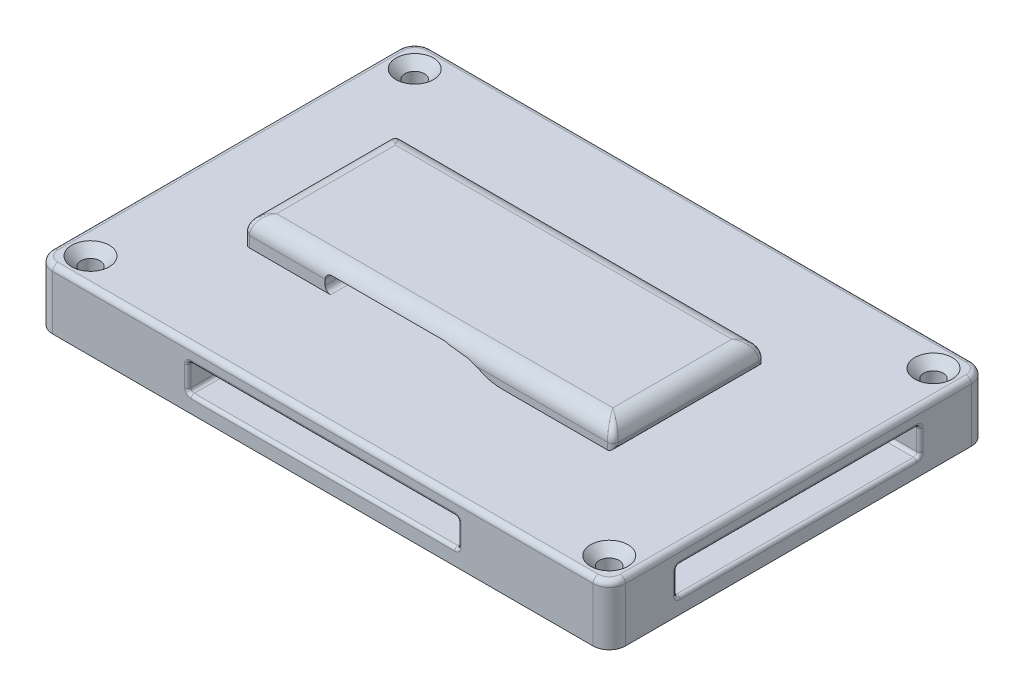
SolidWorks part; units mm, degrees
ref_plane "Alzado" through (0, 0, 0) normal (0, 0, 1) x (1, 0, 0)
ref_plane "Planta" through (0, 0, 0) normal (0, 1, 0) x (1, 0, 0)
ref_plane "Vista lateral" through (0, 0, 0) normal (1, 0, 0) x (0, 0, -1)
sketch "Croquis1" plane through (0, 0, 0) normal (0, 1, 0) x (1, 0, 0)
  line L1 (0, 0) -> (106, 0)
  line L2 (0, 0) -> (0, 70)
  line L3 (0, 70) -> (106, 70)
  line L4 (106, 0) -> (106, 70)
  dimension "D1" = 106
  dimension "D2" = 70
extrude "Saliente-Extruir1" add sketch "Croquis1" along normal blind 11
sketch "Croquis2" plane through (0, 0, 0) normal (0, 0, 1) x (1, 0, 0)
  line L0 (0, 0) -> (0, 3) construction
  line L1 (0, 11) -> (0, 0) construction
  line L2 (0, 3) -> (28, 3) construction
  line L4 (28, 3) -> (78, 3)
  line L5 (28, 3) -> (28, 8)
  line L6 (28, 8) -> (78, 8)
  line L7 (78, 3) -> (78, 8)
  dimension "D1" = 3
  dimension "D2" = 28
  dimension "D3" = 50
  dimension "D4" = 5
extrude "Cortar-Extruir1" cut sketch "Croquis2" against normal through all
sketch "Croquis3" plane through (106, 0, 0) normal (1, 0, 0) x (0, 0, -1)
  line L0 (0, 0) -> (0, 3) construction
  line L1 (0, 3) -> (12.5, 3) construction
  line L3 (12.5, 3) -> (57.5, 3)
  line L4 (12.5, 3) -> (12.5, 8)
  line L5 (12.5, 8) -> (57.5, 8)
  line L6 (57.5, 3) -> (57.5, 8)
  dimension "D1" = 45
  dimension "D2" = 12.5
  dimension "D3" = 5
extrude "Cortar-Extruir2" cut sketch "Croquis3" against normal through all
fillet "Redondeo1" radius 3 4 edges at (0, 5.5, 0) (0, 5.5, -70) (106, 5.5, -70) (106, 5.5, 0)
sketch "Croquis5" plane through (0, 11, 0) normal (0, 1, 0) x (1, 0, 0)
  line L0 (5, 0) -> (5, 5) construction
  line L1 (3, 0) -> (103, 0) construction
  line L2 (5, 5) -> (0, 5) construction
  line L3 (0, 67) -> (0, 3) construction
  line L4 (53, 0) -> (53, 70) construction
  line L5 (103, 70) -> (3, 70) construction
  line L6 (0, 35) -> (106, 35) construction
  line L7 (106, 3) -> (106, 67) construction
  point P15 (101, 5)
  point P16 (5, 5)
  point P17 (101, 65)
  point P18 (5, 65)
  dimension "D1" = 5
  dimension "D2" = 5
hole_wizard "Avellanado para tornillo con cabeza avellanada de clavija hexagonal de M32" positions "Croquis11" profile "Croquis12" countersink size "M3" standard "DIN" end condition through all
sketch "Croquis11" plane through (0, 11, 0) normal (0, 1, 0) x (1, 0, 0)
  point P0 (5, 65)
  point P3 (101, 65)
  point P6 (101, 5)
  point P9 (5, 5)
sketch "Croquis12" plane through (5, 11, -65) normal (1, 0, 0) x (0, 0, 1)
  line L0 (0, 0) -> (0, 11)
  line L1 (0, 11) -> (1.8, 11)
  line L2 (1.8, 11) -> (1.8, 1.67)
  line L3 (1.8, 1.67) -> (3.47, 0)
  line L5 (3.47, 0) -> (0, 0)
  line L6 (-1.8, 1.67) -> (-3.47, 0) construction
  line L11 (0, -6.35) -> (0, 107.95) construction
  dimension "Diámetro de taladro hasta el siguiente" = 3.6
  dimension "Profundidad de taladro hasta el siguiente" = 11
  dimension "Diámetro de avellanado cercano" = 6.94
  dimension "Ángulo de avellanado cercano" = 90
fillet "Redondeo2" radius 1 8 edges at (105.1213, 11, -0.8787) (53, 11, 0) (0.8787, 11, -0.8787) (0, 11, -35) (0.8787, 11, -69.1213) (53, 11, -70) (105.1213, 11, -69.1213) (106, 11, -35)
fillet "Redondeo3" radius 0.6 36 edges at (28, 5.5, 0) (78, 5.5, 0) (0, 5.5, -57.5) (106, 5.5, -57.5) (28, 5.5, -70) (28, 5.5, -57.5) (28, 5.5, -12.5) (0, 5.5, -12.5) (78, 5.5, -12.5) (106, 5.5, -12.5) (78, 5.5, -70) (78, 5.5, -57.5) (53, 8, 0) (78, 8, -6.25) (92, 8, -12.5) (106, 8, -35) (92, 8, -57.5) (78, 8, -63.75) (53, 8, -70) (28, 8, -63.75) (14, 8, -57.5) (0, 8, -35) (14, 8, -12.5) (28, 8, -6.25) (53, 3, 0) (28, 3, -6.25) (14, 3, -12.5) (0, 3, -35) (14, 3, -57.5) (28, 3, -63.75) (53, 3, -70) (78, 3, -63.75) (92, 3, -57.5) (106, 3, -35) (92, 3, -12.5) (78, 3, -6.25)
sketch "Croquis13" plane through (0, 11, 0) normal (0, 1, 0) x (1, 0, 0)
  line L0 (85.6701, 49) -> (85.6701, 21)
  line L1 (103, 69) -> (3, 69) construction
  line L2 (3, 1) -> (103, 1) construction
  line L3 (85.6701, 49) -> (17.4273, 49)
  line L4 (17.4273, 49) -> (17.4273, 21)
  line L5 (17.4273, 21) -> (85.6701, 21)
  dimension "D1" = 20
  dimension "D2" = 20
extrude "Saliente-Extruir2" add sketch "Croquis13" along normal blind 5
sketch "Croquis14" plane through (0, 0, -49) normal (0, 0, -1) x (-1, 0, 0)
  line L0 (-85.6701, 11) -> (-85.6701, 11.75)
  line L1 (-85.6701, 16) -> (-85.6701, 11) construction
  line L2 (-85.6701, 11.75) -> (-65.6701, 11.75)
  line L6 (0, 11) -> (-106, 11) construction
  line L7 (-54.4135, 14) -> (-32.4273, 14)
  line L8 (-32.4273, 14) -> (-32.4273, 11)
  line L9 (-32.4273, 11) -> (-85.6701, 11)
  line L10 (-17.4273, 16) -> (-17.4273, 11) construction
  spline S0 degree 3 poles (-65.6701, 11.75) (-64.7696, 11.7672) (-63.505, 11.7864) (-61.9413, 12.3369) (-60.3454, 12.952) (-59.0672, 13.5347) (-58.063, 13.5686) knots 0 0 0 0 0.34812 0.467839 0.629588 1 1 1 1
  spline S1 degree 3 poles (-58.063, 13.5686) (-56.8514, 13.7672) (-55.6119, 13.7013) (-54.4135, 14) knots 0 0 0 0 1 1 1 1
  dimension "D1" = 0.75
  dimension "D2" = 20
  dimension "D3" = 3
  dimension "D4" = 15
extrude "Cortar-Extruir3" cut sketch "Croquis14" against normal blind 57
fillet "Redondeo4" radius 1 7 edges at (85.6701, 11.75, -35) (32.4273, 14, -35) (32.4273, 11, -35) (17.4273, 13.5, -21) (17.4273, 13.5, -49) (85.6701, 13.875, -21) (85.6701, 13.875, -49)
fillet "Redondeo6" radius 3 8 edges at (85.3772, 16, -21.2929) (51.5487, 16, -21) (17.7202, 16, -21.2929) (17.7202, 16, -48.7071) (51.5487, 16, -49) (85.3772, 16, -48.7071) (17.4273, 16, -35) (85.6701, 16, -35)
